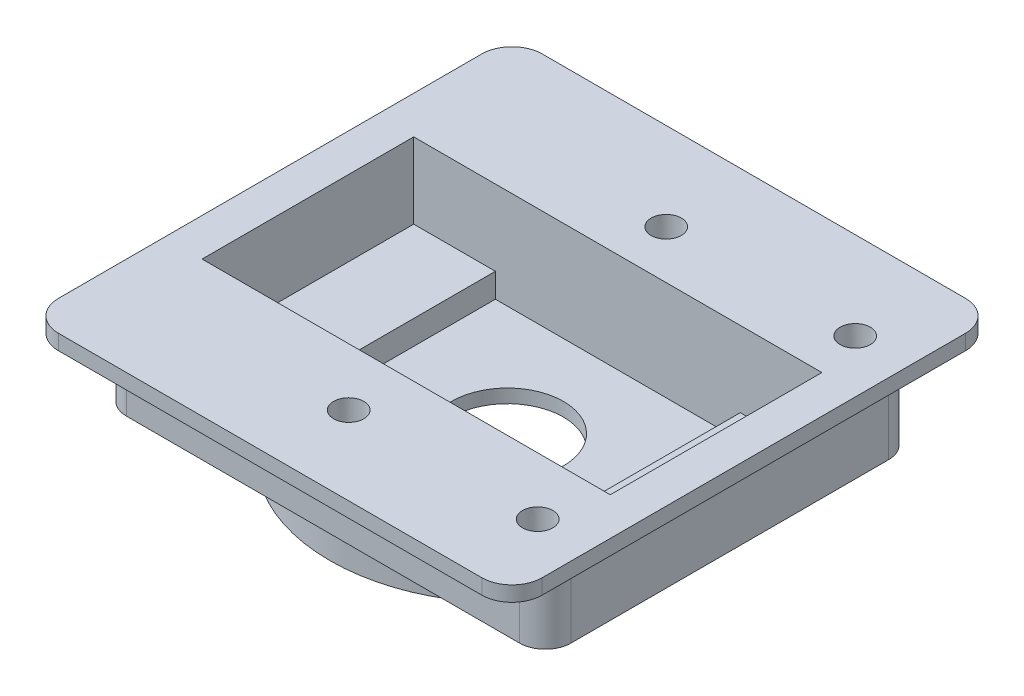
SolidWorks part; units mm, degrees
ref_plane "前视基准面" through (0, 0, 0) normal (0, 0, 1) x (1, 0, 0)
ref_plane "上视基准面" through (0, 0, 0) normal (0, 1, 0) x (1, 0, 0)
ref_plane "右视基准面" through (0, 0, 0) normal (1, 0, 0) x (0, 0, -1)
other "Configuration Table"
sketch "草图1" plane through (0, 0, 0) normal (0, 1, 0) x (1, 0, 0)
  line L1 (-40.5526, -2.4556) -> (-8.5526, -2.4556)
  line L2 (-40.5526, -2.4556) -> (-40.5526, -34.4556)
  line L3 (-40.5526, -34.4556) -> (-8.5526, -34.4556)
  line L4 (-8.5526, -2.4556) -> (-8.5526, -34.4556)
  dimension "D1" = 32
  dimension "D2" = 32
extrude "凸台-拉伸1" add sketch "草图1" along normal blind 1
sketch "草图3" plane through (0, 0, 0) normal (0, -1, 0) x (1, 0, 0)
  line L20 (-9.8526, 8.2556) -> (-9.8526, 29.2556)
  line L21 (-37.5526, 6.5556) -> (-11.5526, 6.5556)
  line L22 (-39.2526, 29.2556) -> (-39.2526, 8.2556)
  line L23 (-11.5526, 30.9556) -> (-37.5526, 30.9556)
  arc A20 (-9.8526, 29.2556) -> (-11.5526, 30.9556) centre (-11.5526, 29.2556) ccw
  arc A21 (-11.5526, 6.5556) -> (-9.8526, 8.2556) centre (-11.5526, 8.2556) ccw
  arc A22 (-39.2526, 8.2556) -> (-37.5526, 6.5556) centre (-37.5526, 8.2556) ccw
  arc A23 (-37.5526, 30.9556) -> (-39.2526, 29.2556) centre (-37.5526, 29.2556) ccw
extrude "凸台-拉伸2" add sketch "草图3" along normal blind 5
sketch "草图2" plane through (0, 1, 0) normal (0, 1, 0) x (1, 0, 0)
  line L0 (-8.5526, -34.4556) -> (-8.5526, -2.4556) construction
  line L1 (-11.0526, -11.4556) -> (-38.0526, -11.4556)
  line L2 (-11.0526, -11.4556) -> (-11.0526, -25.4556)
  line L3 (-11.0526, -25.4556) -> (-38.0526, -25.4556)
  line L4 (-38.0526, -11.4556) -> (-38.0526, -25.4556)
  line L5 (-8.5526, -2.4556) -> (-40.5526, -2.4556) construction
  line L6 (-40.5526, -34.4556) -> (-8.5526, -34.4556) construction
  line L7 (-40.5526, -2.4556) -> (-40.5526, -34.4556) construction
  dimension "D1" = 2.5
  dimension "D2" = 9
  dimension "D3" = 9
  dimension "D4" = 2.5
extrude "切除-拉伸1" cut sketch "草图2" against normal blind 5
sketch "草图4" plane through (0, -5, 0) normal (0, -1, 0) x (1, 0, 0)
  circle A0 centre (-24.5526, 18.7556) radius 11.7476
extrude "凸台-拉伸3" add sketch "草图4" along normal blind 2
sketch "草图5" plane through (0, -7, 0) normal (0, -1, 0) x (1, 0, 0)
  circle A0 centre (-24.5526, 18.7556) radius 4.75
  dimension "D1" = 9.5
extrude "切除-拉伸2" cut sketch "草图5" against normal blind 0.5 draft 37
sketch "草图6" plane through (0, -6.5, 0) normal (0, -1, 0) x (1, 0, 0)
  circle A0 centre (-24.5526, 18.7556) radius 3.7
  dimension "D1" = 7.4
extrude "切除-拉伸3" cut sketch "草图6" against normal through all
fillet "圆角1" radius 2 4 edges at (-40.5526, 0.5, 2.4556) (-8.5526, 0.5, 2.4556) (-40.5526, 0.5, 34.4556) (-8.5526, 0.5, 34.4556)
sketch "草图7" plane through (0, 1, 0) normal (0, 1, 0) x (1, 0, 0)
  circle A0 centre (-24.5526, -8.2556) radius 1
  circle A1 centre (-12.0526, -8.2556) radius 1
  circle A2 centre (-24.5526, -29.2556) radius 1
  circle A3 centre (-12.0526, -29.2556) radius 1
  dimension "D1" = 2
extrude "切除-拉伸4" cut sketch "草图7" against normal blind 4 draft 2
sketch "草图8" plane through (0, -4, 0) normal (0, 1, 0) x (1, 0, 0)
  line L0 (-11.0526, -11.4556) -> (-38.0526, -11.4556) construction
  line L1 (-32.6526, -11.4556) -> (-16.4526, -11.4556)
  line L2 (-32.6526, -11.4556) -> (-32.6526, -25.4556)
  line L3 (-32.6526, -25.4556) -> (-16.4526, -25.4556)
  line L4 (-16.4526, -11.4556) -> (-16.4526, -25.4556)
  line L5 (-38.0526, -25.4556) -> (-11.0526, -25.4556) construction
  line L6 (-38.0526, -11.4556) -> (-38.0526, -25.4556) construction
  line L7 (-11.0526, -25.4556) -> (-11.0526, -11.4556) construction
  dimension "D1" = 5.4
  dimension "D2" = 5.4
extrude "切除-拉伸5" cut sketch "草图8" against normal blind 1.6
